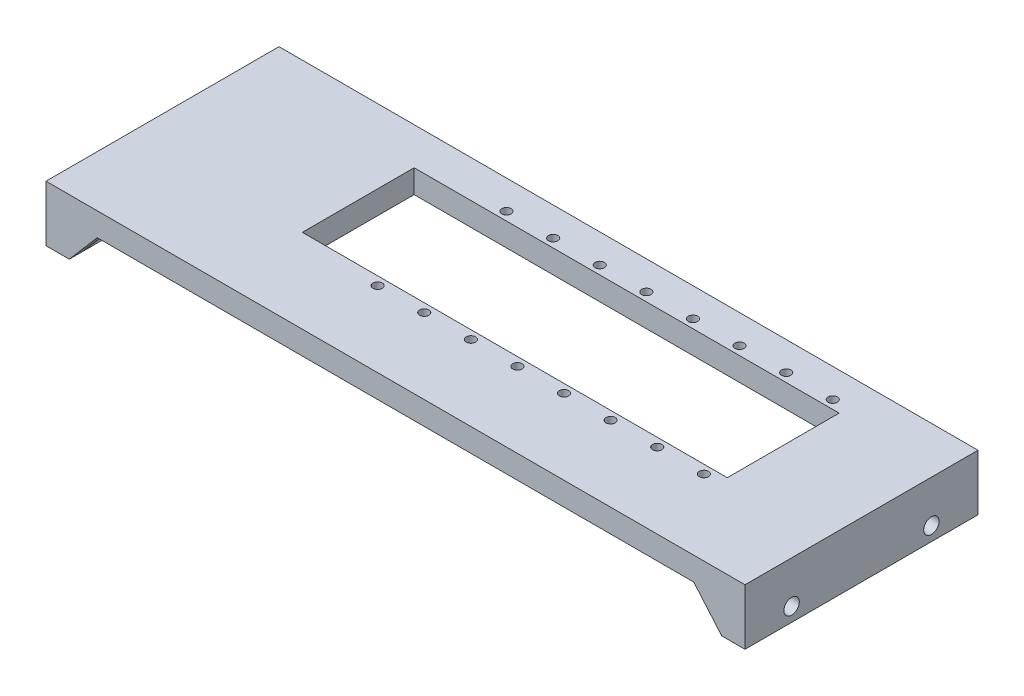
SolidWorks part; units mm, degrees
note: The reader was unsure of these and kept them because the rebuilt part matched: shared geometry of "草图11<3>".
material "PMMA"
ref_plane "前视基准面" through (0, 0, 0) normal (0, 0, 1) x (1, 0, 0)
ref_plane "上视基准面" through (0, 0, 0) normal (0, 1, 0) x (1, 0, 0)
ref_plane "右视基准面" through (0, 0, 0) normal (1, 0, 0) x (0, 0, -1)
sketch "草图1" plane through (0, 0, 0) normal (0, 0, 1) x (1, 0, 0)
  line L0 (-75, 0) -> (75, 0)
  line L1 (75, 0) -> (75, -12)
  line L2 (75, -12) -> (70, -12)
  line L3 (70, -12) -> (70, -5)
  line L4 (70, -5) -> (-70, -5)
  line L5 (-70, -5) -> (-70, -12)
  line L6 (-70, -12) -> (-75, -12)
  line L7 (-75, -12) -> (-75, 0)
  line L8 (0, -7.4248) -> (0, 9.2484) construction
  dimension "D1" = 5
  dimension "D2" = 5
  dimension "D3" = 150
  dimension "D4" = 12
  dimension "D5" = 12
extrude "凸台-拉伸2" add sketch "草图1" along normal blind 40
sketch "草图3" plane through (-70, 0, 0) normal (1, 0, 0) x (0, 0, -1)
  line L0 (0, 0) -> (0, -12) construction
  line L1 (-40, -12) -> (0, -12) construction
  circle A0 centre (-10, -9) radius 1.65
  dimension "D2" = 3.3
  dimension "D1" = 3
  dimension "D3" = 10
extrude "切除-拉伸1" cut sketch "草图3" against normal through all both and the other way through all
sketch "草图4" plane through (0, 0, 0) normal (0, 0, -1) x (-1, 0, 0)
  line L0 (64, -5) -> (70, -12)
  line L1 (70, -5) -> (-70, -5) construction
  line L2 (64, -5) -> (70, -5)
  line L4 (70, -5) -> (70, -12)
  dimension "D1" = 6
extrude "凸台-拉伸3" add sketch "草图4" against normal blind 3
sketch "草图5" plane through (0, -5, 0) normal (0, -1, 0) x (1, 0, 0)
  line L0 (70, 20) -> (-70, 20) construction
  line L1 (70, 40) -> (70, 0) construction
  line L2 (-70, 40) -> (-70, 3) construction
ref_plane "基准面3" through (0, 0, 20) normal (0, 0, 1) x (1, 0, 0)
mirror "镜向1" about plane through (0, 0, 20) normal (0, 0, 1) of "凸台-拉伸3"
sketch "草图6" plane through (0, 0, 0) normal (0, 1, 0) x (1, 0, 0)
  line L0 (0, -40) -> (0, 0) construction
  line L1 (75, -40) -> (-75, -40) construction
mirror "镜向2" about plane through (0, 0, 0) normal (1, 0, 0) of "镜向1", "凸台-拉伸3"
sketch "草图7" plane through (0, -5, 0) normal (0, -1, 0) x (1, 0, 0)
  line L0 (70, 20) -> (-70, 20) construction
  line L1 (53.2, 22.4) -> (53.2, 17.6)
  line L5 (53.2, 22.4) -> (34, 8) construction
  line L6 (34, 32) -> (53.2, 17.6) construction
  line L7 (50, 40) -> (50, 0) construction
  line L8 (75, 40) -> (75, 0) construction
  line L9 (-64, 40) -> (64, 40) construction
  line L10 (-64, 0) -> (64, 0) construction
  line L11 (34, 32) -> (-37.9962, 32)
  line L12 (-37.9962, 32) -> (-37.9962, 8)
  line L13 (-37.9962, 8) -> (34, 8)
  line L14 (34, 32) -> (53.2, 32)
  line L15 (53.2, 32) -> (53.2, 22.4)
  line L16 (53.2, 17.6) -> (53.2, 8)
  line L17 (53.2, 8) -> (34, 8)
  point P0 (50, 20)
  dimension "D3" = 25
extrude "切除-拉伸2" cut sketch "草图7" against normal blind 5 contours L1 L16 L17 L13 L12 L11 L14 L15
sketch "草图10" plane through (0, -5, 0) normal (0, -1, 0) x (1, 0, 0)
  line L0 (56, 33.835) -> (56, 6.165) construction
  line L1 (50, 33.835) -> (50, 6.165) construction
  line L2 (40, 33.835) -> (40, 25.79) construction
  line L3 (75, 40) -> (75, 0) construction
  line L4 (56, 33.835) -> (-27.9962, 33.835) construction
  line L5 (53.2, 20) -> (-37.9962, 20) construction
  line L6 (53.2, 32) -> (53.2, 8) construction
  line L7 (-37.9962, 32) -> (-37.9962, 8) construction
  line L8 (56, 6.165) -> (-27.9962, 6.165) construction
  circle A0 centre (50, 33.835) radius 1
  circle A2 centre (40, 33.835) radius 1
  circle A3 centre (30, 33.835) radius 1
  circle A4 centre (20, 33.835) radius 1
  circle A5 centre (10, 33.835) radius 1
  circle A6 centre (0, 33.835) radius 1
  circle A7 centre (-10, 33.835) radius 1
  circle A8 centre (-20, 33.835) radius 1
  circle A9 centre (50, 6.165) radius 1
  circle A10 centre (40, 6.165) radius 1
  circle A11 centre (30, 6.165) radius 1
  circle A12 centre (20, 6.165) radius 1
  circle A13 centre (10, 6.165) radius 1
  circle A14 centre (0, 6.165) radius 1
  circle A15 centre (-10, 6.165) radius 1
  circle A16 centre (-20, 6.165) radius 1
  dimension "D2" = 2
  dimension "D3" = 25
  dimension "D1" = 8
extrude "切除-拉伸3" cut sketch "草图10" against normal blind 5
ref_plane "基准面4" through (0, 0, 40) normal (0, 0, 1) x (1, 0, 0)
sketch "草图11" plane through (0, 0, 40) normal (0, 0, 1) x (1, 0, 0)
  line L0 (-70, -12) -> (-70, -5)
  line L1 (-70, -5) -> (-64, -5)
  line L2 (64, -5) -> (70, -5)
  line L3 (70, -5) -> (70, -12)
  line L8 (-64, -5) -> (64, -5)
  line L9 (64, -5) -> (70, -12)
  line L10 (70, -12) -> (75, -12)
  line L11 (75, -12) -> (75, 0)
  line L12 (75, 0) -> (-75, 0)
  line L13 (-75, 0) -> (-75, -12)
  line L14 (-75, -12) -> (-70, -12)
  line L15 (-70, -12) -> (-64, -5)
  line L16 (-64, -5) -> (64, -5)
  line L17 (64, -5) -> (70, -12)
  line L18 (70, -12) -> (75, -12)
  line L19 (75, -12) -> (75, 0)
  line L20 (75, 0) -> (-75, 0)
  line L21 (-75, 0) -> (-75, -12)
  line L22 (-75, -12) -> (-70, -12)
  line L23 (-70, -12) -> (-64, -5)
  dimension "D1" = 0
extrude "凸台-拉伸4" add sketch "草图11" along normal blind 10 contours L21 L22 L0 L1 L16 L2 L3 L18 L19 L20
extrude "切除-拉伸4" cut sketch "草图11<3>" against normal up to next and the other way blind 7 contours L0 L23 L1 | L2 L17 L3
sketch "草图11<3>" plane through (0, 0, 40) normal (0, 0, 1) x (1, 0, 0) same geometry as "草图11"
sketch "草图12" plane through (0, 0, 0) normal (1, 0, 0) x (0, 0, -1)
  line L0 (-25, 0) -> (-25, -16.3745) construction
  line L4 (0, -12) -> (0, 0)
  line L5 (0, 0) -> (-50, 0)
  line L6 (-50, 0) -> (-50, -12)
  line L7 (-50, -12) -> (0, -12)
  line L8 (0, -12) -> (0, 0)
  line L9 (0, 0) -> (-50, 0)
  line L10 (-50, 0) -> (-50, -12)
  line L11 (-50, -12) -> (0, -12)
  circle A0 centre (-10, -9) radius 1.65 construction
  circle A1 centre (-10, -9) radius 1.65
  circle A2 centre (-40, -9) radius 1.65
  dimension "D1" = 0
extrude "切除-拉伸5" cut sketch "草图12" against normal through all both and the other way through all contours A2
